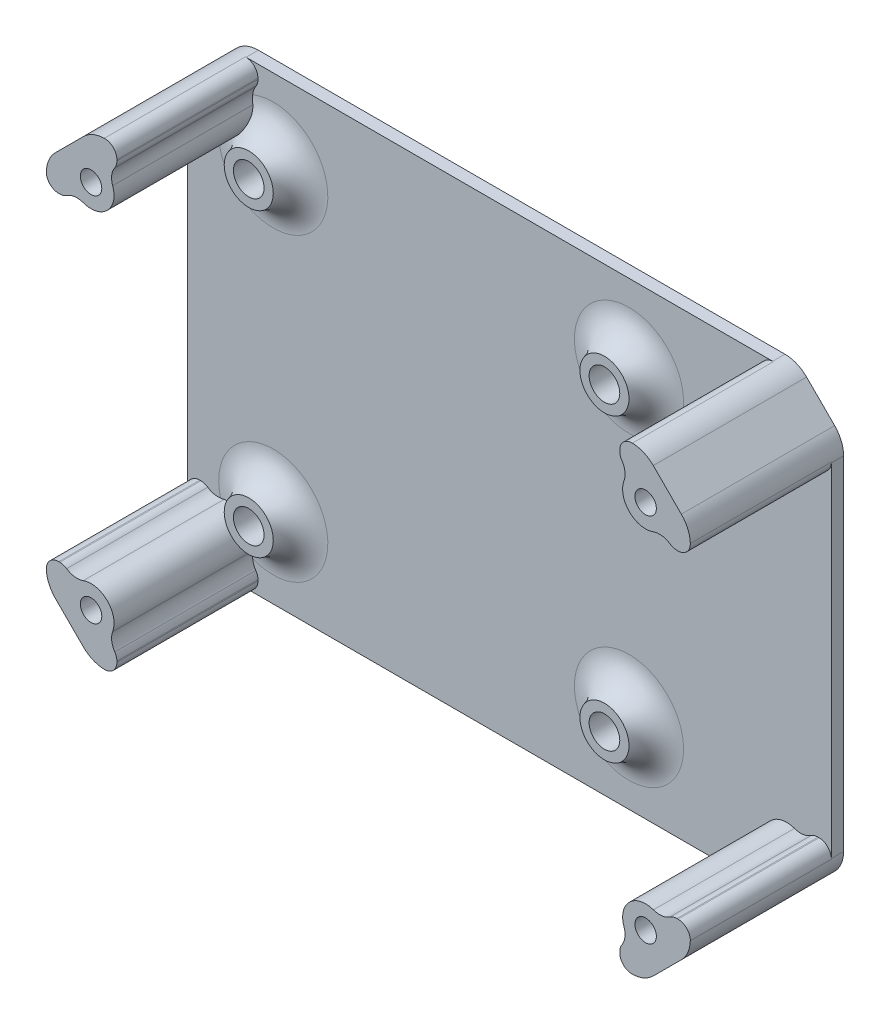
SolidWorks part; units mm, degrees
material "ABS"
ref_plane "Спереди" through (0, 0, 0) normal (0, 0, 1) x (1, 0, 0)
ref_plane "Сверху" through (0, 0, 0) normal (0, 1, 0) x (1, 0, 0)
ref_plane "Справа" through (0, 0, 0) normal (1, 0, 0) x (0, 0, -1)
sketch "Эскиз1" plane through (0, 0, 0) normal (0, 0, 1) x (1, 0, 0)
  line L0 (-52.5, 30) -> (-45, 37.5)
  line L1 (-45, 37.5) -> (45, 37.5)
  line L2 (-52.5, 30) -> (-52.5, -30)
  line L3 (-45, -37.5) -> (45, -37.5)
  line L4 (52.5, 30) -> (52.5, -30)
  line L5 (-52.5, 37.5) -> (52.5, -37.5) construction
  line L6 (-52.5, -37.5) -> (52.5, 37.5) construction
  line L7 (45, 37.5) -> (52.5, 30)
  line L8 (45, -37.5) -> (52.5, -30)
  line L9 (-52.5, -30) -> (-45, -37.5)
  point P0 (0, 0)
  dimension "D1" = 75
  dimension "D2" = 105
extrude "Бобышка-Вытянуть1" add sketch "Эскиз1" along normal blind 25
sketch "Эскиз2" plane through (0, 0, 25) normal (0, 0, 1) x (1, 0, 0)
  line L0 (-48.75, 33.75) -> (-38.4079, 23.4079) construction
  line L1 (-45, 37.5) -> (-52.5, 30) construction
  line L2 (-52.5, 0) -> (52.5, 0) construction
  line L3 (-52.5, 30) -> (-52.5, -30) construction
  line L4 (52.5, -30) -> (52.5, 30) construction
  line L5 (0, 37.5) -> (0, -37.5) construction
  line L6 (45, 37.5) -> (-45, 37.5) construction
  line L7 (-45, -37.5) -> (45, -37.5) construction
  line L8 (48.75, 33.75) -> (38.4079, 23.4079) construction
  line L9 (48.75, -33.75) -> (38.4079, -23.4079) construction
  line L10 (-48.75, -33.75) -> (-38.4079, -23.4079) construction
  circle A0 centre (-45.2145, 30.2145) radius 1.75
  circle A1 centre (45.2145, 30.2145) radius 1.75
  circle A2 centre (45.2145, -30.2145) radius 1.75
  circle A3 centre (-45.2145, -30.2145) radius 1.75
  dimension "D1" = 3.5
  dimension "D2" = 5
extrude "Вырез-Вытянуть1" cut sketch "Эскиз2" against normal blind 34
shell "Оболочка1" thickness 2 removed face at (-46.9645, -30.2145, 25)
fillet "Скругление1" radius 10 8 edges at (-45.7448, -33.9268, 13.5) (-48.9268, -30.7448, 13.5) (48.9268, -30.7448, 13.5) (45.7448, -33.9268, 13.5) (45.7448, 33.9268, 13.5) (48.9268, 30.7448, 13.5) (-45.7448, 33.9268, 13.5) (-48.9268, 30.7448, 13.5)
fillet "Скругление2" radius 3 8 edges at (-50.5, 29.1716, 13.5) (-44.1716, 35.5, 13.5) (-44.1716, -35.5, 13.5) (-50.5, -29.1716, 13.5) (44.1716, -35.5, 13.5) (50.5, -29.1716, 13.5) (50.5, 29.1716, 13.5) (44.1716, 35.5, 13.5)
fillet "Скругление3" radius 5 8 edges at (-52.5, 30, 12.5) (-45, 37.5, 12.5) (45, 37.5, 12.5) (52.5, 30, 12.5) (52.5, -30, 12.5) (45, -37.5, 12.5) (-52.5, -30, 12.5) (-45, -37.5, 12.5)
ref_plane "Плоскость1" through (42.9289, -37.5, 25) normal (1, 0, 0) x (0, 0, -1)
sketch "Эскиз4" plane through (0, 0, 25) normal (0, 0, 1) x (1, 0, 0)
  line L1 (-41, 63.3728) -> (41, 63.3728)
  line L2 (-41, 63.3728) -> (-41, -63.3728)
  line L3 (-41, -63.3728) -> (41, -63.3728)
  line L4 (41, 63.3728) -> (41, -63.3728)
  line L5 (-41, 63.3728) -> (41, -63.3728) construction
  line L6 (-41, -63.3728) -> (41, 63.3728) construction
  point P0 (0, 0)
  dimension "D1" = 82
extrude "Вырез-Вытянуть2" cut sketch "Эскиз4" against normal up to surface (23 mm away) up to face at (0, 0, 2)
fillet "Скругление4" radius 2 8 edges at (41, -34.6057, 13.5) (41, -37.5, 13.5) (-41, -34.6057, 13.5) (-41, -37.5, 13.5) (-41, 34.6057, 13.5) (-41, 37.5, 13.5) (41, 34.6057, 13.5) (41, 37.5, 13.5)
sketch "Эскиз5" plane through (0, 0, 25) normal (0, 0, 1) x (1, 0, 0)
  line L1 (-86.9479, 26) -> (86.9479, 26)
  line L2 (-86.9479, 26) -> (-86.9479, -26)
  line L3 (-86.9479, -26) -> (86.9479, -26)
  line L4 (86.9479, 26) -> (86.9479, -26)
  line L5 (-86.9479, 26) -> (86.9479, -26) construction
  line L6 (-86.9479, -26) -> (86.9479, 26) construction
  point P0 (0, 0)
  dimension "D1" = 52
extrude "Вырез-Вытянуть3" cut sketch "Эскиз5" against normal up to surface (23 mm away) up to face at (0, 0, 2)
fillet "Скругление5" radius 2 8 edges at (49.6057, -26, 13.5) (52.5, -26, 13.5) (49.6057, 26, 13.5) (52.5, 26, 13.5) (-49.6057, -26, 13.5) (-52.5, -26, 13.5) (-49.6057, 26, 13.5) (-52.5, 26, 13.5)
sketch "Эскиз6" plane through (0, 0, 2) normal (0, 0, 1) x (1, 0, 0)
  line L0 (-52.5, 0) -> (52.5, 0) construction
  line L1 (-52.5, -27.9289) -> (-52.5, 27.9289) construction
  line L2 (52.5, 27.9289) -> (52.5, -27.9289) construction
  line L4 (-38.5, 24.5) -> (19.5, 24.5) construction
  line L5 (-38.5, 24.5) -> (-38.5, -24.5) construction
  line L6 (-38.5, -24.5) -> (19.5, -24.5) construction
  line L7 (19.5, 24.5) -> (19.5, -24.5) construction
  line L8 (-38.5, 24.5) -> (19.5, -24.5) construction
  line L9 (-38.5, -24.5) -> (19.5, 24.5) construction
  circle A0 centre (-38.5, 24.5) radius 4
  circle A1 centre (19.5, 24.5) radius 4
  circle A2 centre (19.5, -24.5) radius 4
  circle A3 centre (-38.5, -24.5) radius 4
  point P6 (-9.5, 0)
  dimension "D3" = 8
  dimension "D1" = 58
  dimension "D2" = 49
  dimension "D4" = 43
extrude "Бобышка-Вытянуть2" add sketch "Эскиз6" along normal blind 4
sketch "Эскиз7" plane through (0, 0, 6) normal (0, 0, 1) x (1, 0, 0)
  circle A0 centre (-38.5, 24.5) radius 2.5
  circle A1 centre (19.5, 24.5) radius 2.5
  circle A2 centre (19.5, -24.5) radius 2.5
  circle A3 centre (-38.5, -24.5) radius 2.5
  dimension "D1" = 5
extrude "Вырез-Вытянуть4" cut sketch "Эскиз7" against normal blind 6
fillet "Скругление6" radius 5 4 edges at (-42.5, 24.5, 2) (-42.5, -24.5, 2) (15.5, -24.5, 2) (15.5, 24.5, 2)
